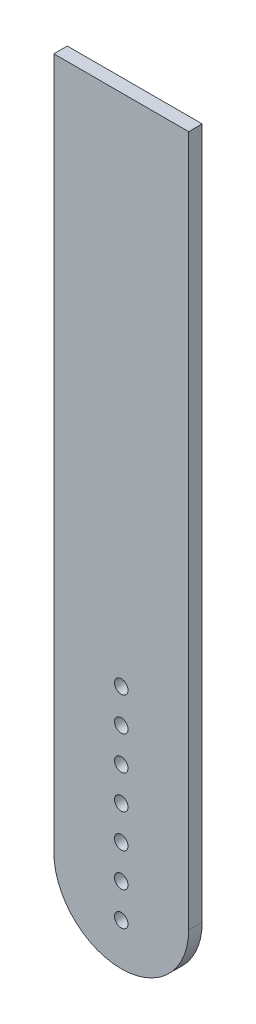
SolidWorks part; units mm, degrees
other "Markup1"
sketch "Sketch7" plane through (-20, 225, -2) normal (-0.1146, 0.1086, -0.9875) x (-0.991, 0.0573, 0.1213)
ref_plane "Front Plane" through (0, 0, 0) normal (0, 0, 1) x (1, 0, 0)
ref_plane "Top Plane" through (0, 0, 0) normal (0, 1, 0) x (1, 0, 0)
ref_plane "Right Plane" through (0, 0, 0) normal (1, 0, 0) x (0, 0, -1)
sketch "Sketch1" plane through (0, 0, 0) normal (0, 1, 0) x (1, 0, 0)
  line L1 (-20, 2) -> (20, 2)
  line L2 (-20, 2) -> (-20, -2)
  line L3 (-20, -2) -> (20, -2)
  line L4 (20, 2) -> (20, -2)
  line L5 (-20, 2) -> (20, -2) construction
  line L6 (-20, -2) -> (20, 2) construction
  point P0 (0, 0)
extrude "Boss-Extrude1" add sketch "Sketch1" along normal blind 225
fillet "Fillet1" radius 20 2 edges at (-20, 0, 0) (20, 0, 0)
sketch "Sketch2" plane through (0, 0, 2) normal (0, 0, 1) x (1, 0, 0)
  circle A0 centre (0, 12.5) radius 2
  dimension "D1" = 12.5
extrude "Cut-Extrude1" cut sketch "Sketch2" against normal through all
pattern_linear "LPattern1" count 7 spacing 10 along (0, 1, 0) of "Cut-Extrude1"
sketch "Sketch6" plane through (0, 0, -2) normal (0, 0, -1) x (-1, 0, 0)
  line L1 (-6.5, 1.0857) -> (-8.5, 1.0857)
  line L2 (-6.5, 1.0857) -> (-6.5, 101.0857)
  line L3 (-6.5, 101.0857) -> (-8.5, 101.0857)
  line L4 (-8.5, 1.0857) -> (-8.5, 101.0857)
  line L5 (-7.5, 101.0857) -> (-7.5, 1.0857) construction
  line L6 (-6.5, 51.0857) -> (-8.5, 51.0857) construction
  line L7 (-20, 225) -> (-20, 20) construction
  arc A0 (-20, 20) -> (0, 0) centre (0, 20) ccw construction
  point P524 (-7.5, 51.0857)
  dimension "D1" = 2
  dimension "D2" = 12.5
  dimension "D3" = 100
extrude "Cut-Extrude3" cut sketch "Sketch6" against normal blind 2 contours L3 L4 L1 L2
fillet "Fillet2" radius 1 2 edges at (8.5, 101.0857, -1) (6.5, 101.0857, -1)
mirror "Mirror1" about plane through (0, 0, 0) normal (1, 0, 0) of "Fillet2", "Cut-Extrude3"
sketch "Sketch8" plane through (0, 0, -2) normal (0, 0, -1) x (-1, 0, 0)
  line L0 (-20, 225) -> (20, 225) construction
  line L1 (-20, 225) -> (-20, 20) construction
  line L2 (20, 225) -> (20, 20) construction
  circle A0 centre (-15, 215) radius 1.8
  circle A1 centre (15, 215) radius 1.8
  dimension "D1" = 10
  dimension "D3" = 10
  dimension "D2" = 5
  dimension "D4" = 5
